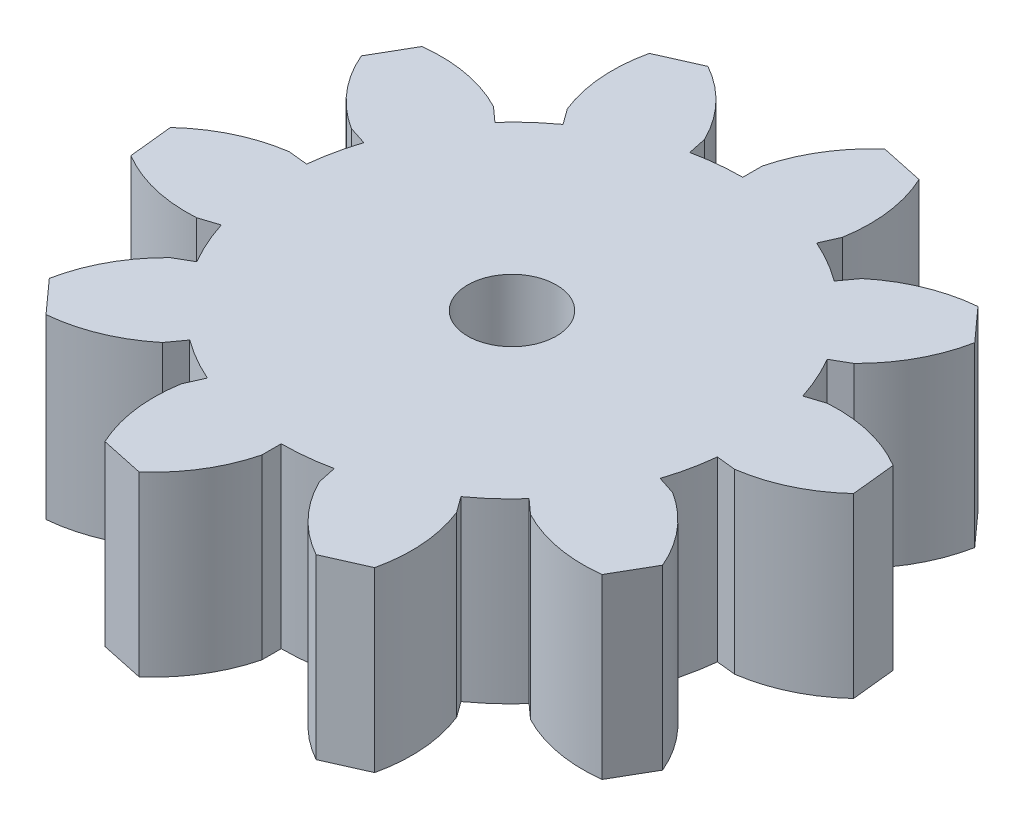
SolidWorks part; units mm, degrees
ref_plane "Front Plane" through (0, 0, 0) normal (0, 0, 1) x (1, 0, 0)
ref_plane "Top Plane" through (0, 0, 0) normal (0, 1, 0) x (1, 0, 0)
ref_plane "Right Plane" through (0, 0, 0) normal (1, 0, 0) x (0, 0, -1)
sketch "Sketch1" plane through (0, 0, 0) normal (0, 1, 0) x (1, 0, 0)
  line L0 (0, 14.0954) -> (0, 0) construction
  line L1 (0, 0) -> (14.0954, 0) construction
  line L2 (0, 0) -> (7.0477, 12.207) construction
  line L3 (0, 0) -> (12.207, 7.0477) construction
  line L4 (0, 0) -> (3.1187, 14.6722) construction
  line L5 (7.0477, 12.207) -> (0.6561, 15.8971) construction
  line L6 (12.207, 7.0477) -> (4.8266, 19.8308) construction
  line L7 (14.0954, 0) -> (14.0954, 22.141) construction
  line L8 (0, 0) -> (6.101, 13.7032) construction
  line L9 (0, 14.0954) -> (0, 13)
  line L10 (5.7331, 12.8768) -> (5.2876, 11.8761)
  line L11 (3.1187, 14.6722) -> (4.1287, 19.4241) construction
  line L12 (5.0737, 17.8579) -> (2.6284, 18.3776)
  circle A5 centre (0, 0) radius 12.5 construction
  circle A6 centre (0, 0) radius 14.0954 construction
  circle A7 centre (0, 0) radius 15 construction
  circle A8 centre (0, 0) radius 17 construction
  circle A9 centre (0, 0) radius 13
  arc A11 (0, 14.0954) -> (4.1287, 19.4241) centre (8.1732, 12.0266) cw
  arc A12 (5.7331, 12.8768) -> (4.1287, 19.4241) centre (-2.5749, 14.3112) ccw
  spline S0 degree 3 poles (0, 14.0954) (1.2399, 19.8677) (9.3388, 22.1485) (14.0954, 22.141) knots 0 0 0 0 1 1 1 1 construction
  spline S1 degree 3 poles (5.7331, 12.8768) (6.9482, 18.6543) (0.4772, 24.0321) (-3.8712, 25.9599) knots 0 0 0 0 1 1 1 1 construction
  point P23 (1.3278, 16.9481)
  point P26 (5.6804, 16.0229)
  point P27 (4.1287, 19.4241)
  point P33 (3.851, 18.1178)
  dimension "Root Circle" = 25
  dimension "Base" = 28.1908
  dimension "Pitch" = 30
  dimension "adendum" = 34
  dimension "clearance" = 26
  dimension "D1" = 30
  dimension "D2" = 30
  dimension "involute4" = 22.141
  dimension "involute3" = 14.7607
  dimension "involute2" = 7.3803
  dimension "D3" = 24
  dimension "D4" = 12
  dimension "D5" = 2.5
extrude "Boss-Extrude2" add sketch "Sketch1" along normal blind 10 contours L10 A12 A11 L9 A9 region at (3.2053, 0, -15.0798)
ref_axis "Axis1" through (0, 10.5, 0) along (0, -1, 0)
pattern_circular "CirPattern1" count 10 over 360 about axis through (0, 10.5, 0) along (0, -1, 0) of "Boss-Extrude2"
extrude "Boss-Extrude3" add sketch "Sketch1<5>" along normal blind 10 contours A9
sketch "Sketch1<5>" plane through (0, 0, 0) normal (0, 1, 0) x (1, 0, 0) same geometry as "Sketch1"
sketch "Sketch2" plane through (0, 0, 0) normal (0, -1, 0) x (1, 0, 0)
  circle A0 centre (0, 0) radius 2.5
  dimension "D1" = 5
extrude "Cut-Extrude1" cut sketch "Sketch2" against normal through all
equation "\"Module\"= 2"
equation "\"Number of teeeeeth\"= 15"
equation "\"Pressure ange\"= 20deg"
equation "\"Base@Sketch1\" = \"Pitch@Sketch1\" * cos ( \"Pressure ange\" )"
equation "\"Root Circle@Sketch1\" = \"Pitch@Sketch1\" - ( ( \"Module\" * 1.25 ) * 2 )"
equation "\"Pitch@Sketch1\"= \"Module\" * \"Number of teeeeeth\""
equation "\"adendum@Sketch1\" = \"Pitch@Sketch1\" + ( \"Module\" * 2 )"
equation "\"clearance@Sketch1\"= \"Pitch@Sketch1\" - ( \"Module\" * 2 )"
equation "\"D1@Sketch1\"=90/3"
equation "\"involute4@Sketch1\" = \"Base@Sketch1\" * pi / 4"
equation "\"involute3@Sketch1\"= \"involute4@Sketch1\" / 3 * 2"
equation "\"involute2@Sketch1\"= \"involute4@Sketch1\" / 3"
equation "\"D3@Sketch1\"=360 / \"Number of teeeeeth\""
